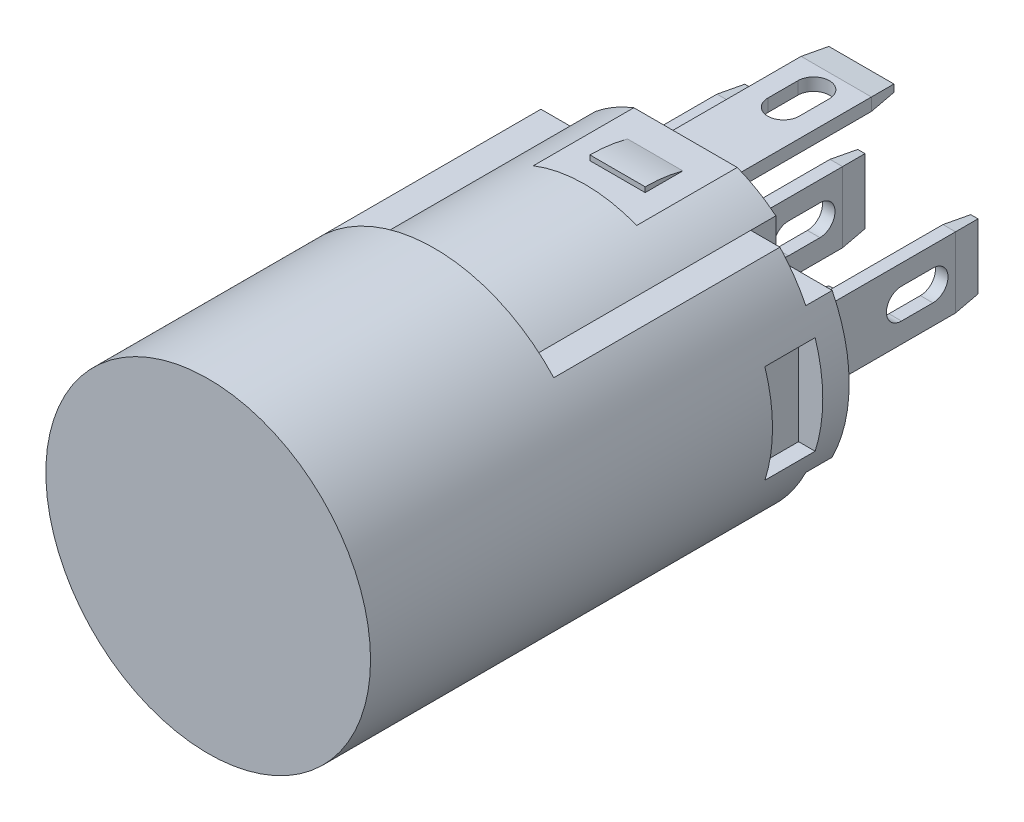
SolidWorks part; units mm, degrees
ref_plane "Front Plane" through (0, 0, 0) normal (0, 0, 1) x (1, 0, 0)
ref_plane "Top Plane" through (0, 0, 0) normal (0, 1, 0) x (1, 0, 0)
ref_plane "Right Plane" through (0, 0, 0) normal (1, 0, 0) x (0, 0, -1)
sketch "Sketch1" plane through (0, 0, 0) normal (0, 0, 1) x (1, 0, 0)
  circle A10 centre (0, 0) radius 6.4624
  dimension "D1" = 12.9248
extrude "Boss-Extrude1" add sketch "Sketch1" against normal blind 19
sketch "Sketch2" plane through (0, 0, -19) normal (0, 0, -1) x (-1, 0, 0)
  line L1 (-7.5854, -4.375) -> (7.5854, -4.375)
  line L2 (-7.5854, -4.375) -> (-7.5854, 4.375)
  line L3 (-7.5854, 4.375) -> (7.5854, 4.375)
  line L4 (7.5854, -4.375) -> (7.5854, 4.375)
  line L5 (-7.5854, -4.375) -> (7.5854, 4.375) construction
  line L6 (-7.5854, 4.375) -> (7.5854, -4.375) construction
  circle A3 centre (0, 0) radius 5.6624
  circle A4 centre (0, 0) radius 5.6624
  circle A5 centre (0, 0) radius 6.4624
  circle A6 centre (0, 0) radius 6.4624
  circle M4 centre (0, 0) radius 6.4624
  dimension "D2" = 8.75
  dimension "D1" = 0.8
  dimension "D3" = 0
extrude "Cut-Extrude1" cut sketch "Sketch2" against normal blind 10 contours A4 L3 M4 | A4 L1 M4 region at (4.1755, -4.4724, -19) region at (0, 6.365, -19)
sketch "Sketch3" plane through (0, 0, -19) normal (0, 0, -1) x (-1, 0, 0)
  line L0 (-4.2468, 1.4) -> (-4.7468, -1.4) construction
  line L1 (-0.25, -1.4) -> (0.25, -1.4)
  line L2 (-0.25, -1.4) -> (-0.25, 1.4)
  line L3 (-0.25, 1.4) -> (0.25, 1.4)
  line L4 (0.25, -1.4) -> (0.25, 1.4)
  line L5 (-0.25, -1.4) -> (0.25, 1.4) construction
  line L6 (-0.25, 1.4) -> (0.25, -1.4) construction
  line L7 (0, 3.7558) -> (0, 4.375) construction
  line L8 (4.2468, -1.4) -> (4.7468, -1.4)
  line L9 (4.2468, -1.4) -> (4.2468, 1.4)
  line L10 (4.2468, 1.4) -> (4.7468, 1.4)
  line L11 (4.7468, -1.4) -> (4.7468, 1.4)
  line L12 (4.2468, -1.4) -> (4.7468, 1.4) construction
  line L13 (4.2468, 1.4) -> (4.7468, -1.4) construction
  line L14 (-4.2468, -1.4) -> (-4.7468, 1.4) construction
  line L15 (-4.7468, -1.4) -> (-4.7468, 1.4)
  line L16 (-4.2468, 1.4) -> (-4.7468, 1.4)
  line L17 (-4.2468, -1.4) -> (-4.2468, 1.4)
  line L18 (-4.2468, -1.4) -> (-4.7468, -1.4)
  line L19 (-3.5947, -4.375) -> (3.5947, -4.375)
  line L20 (-4.2468, 0) -> (-2.8967, 0) construction
  line L25 (-1.4, -4.375) -> (1.4, -4.375)
  line L26 (-1.4, -4.375) -> (-1.4, -3.875)
  line L27 (-1.4, -3.875) -> (1.4, -3.875)
  line L28 (1.4, -4.375) -> (1.4, -3.875)
  line L30 (1.4, 4.375) -> (1.4, 3.875)
  line L31 (-1.4, 3.875) -> (1.4, 3.875)
  line L32 (-1.4, 4.375) -> (-1.4, 3.875)
  line L33 (-1.4, 4.375) -> (1.4, 4.375)
  point P0 (0, 0)
  point P8 (4.4968, 0)
  point P17 (-4.4968, 0)
  point P22 (0, -4.375)
  point P27 (0, -3.875)
  point P36 (0, 4.375)
  dimension "D1" = 2.8
  dimension "D2" = 0.5
  dimension "D3" = 0.5
  dimension "D4" = 3.9968
  dimension "D5" = 2.8
  dimension "D6" = 0.5
extrude "Boss-Extrude2" add sketch "Sketch3" along normal blind 7 separate body contours L18 L17 L16 L15 | L33 L32 L31 L30 | L19 L28 L27 L26 | L8 L11 L10 L9 | L1 L4 L3 L2 region at (0, 0, -19) region at (-4.4968, 0, -19) region at (4.4968, 0, -19) region at (0, -4.125, -19) region at (0, 4.125, -19)
chamfer "Chamfer1" distance 1 angle 6 4 edges at (-4.2468, 0, -26) (-4.4968, 1.4, -26) (-4.7468, 0, -26) (-4.4968, -1.4, -26) first distance on face at (-4.2468, 0, -22.5) first distance on face at (-4.4968, 1.4, -22.5) first distance on face at (-4.7468, 0, -22.5) first distance on face at (-4.4968, -1.4, -22.5)
chamfer "Chamfer2" distance 1 angle 6 4 edges at (4.7468, 0, -26) (4.4968, 1.4, -26) (4.2468, 0, -26) (4.4968, -1.4, -26) first distance on face at (4.7468, 0, -22.5) first distance on face at (4.4968, 1.4, -22.5) first distance on face at (4.2468, 0, -22.5) first distance on face at (4.4968, -1.4, -22.5)
chamfer "Chamfer3" distance 1 angle 6 4 edges at (0.25, 0, -26) (0, 1.4, -26) (-0.25, 0, -26) (0, -1.4, -26) first distance on face at (0.25, 0, -22.5) first distance on face at (0, 1.4, -22.5) first distance on face at (-0.25, 0, -22.5) first distance on face at (0, -1.4, -22.5)
chamfer "Chamfer4" distance 1 angle 6 4 edges at (-1.4, 4.125, -26) (0, 3.875, -26) (1.4, 4.125, -26) (0, 4.375, -26) first distance on face at (-1.4, 4.125, -22.5) first distance on face at (0, 3.875, -22.5) first distance on face at (1.4, 4.125, -22.5) first distance on face at (0, 4.375, -22.5)
chamfer "Chamfer5" distance 1 angle 6 4 edges at (1.4, -4.125, -26) (0, -3.875, -26) (-1.4, -4.125, -26) (0, -4.375, -26) first distance on face at (1.4, -4.125, -22.5) first distance on face at (0, -3.875, -22.5) first distance on face at (-1.4, -4.125, -22.5) first distance on face at (0, -4.375, -22.5)
sketch "Sketch4" plane through (4.7468, 0, 0) normal (1, 0, 0) x (0, 0, -1)
  line L0 (22.85, 0) -> (24.1, 0) construction
  line L1 (22.85, 0.6) -> (24.1, 0.6)
  line L2 (22.85, -0.6) -> (24.1, -0.6)
  line L3 (25, -1.4) -> (25, 1.4) construction
  arc A0 (22.85, 0.6) -> (22.85, -0.6) centre (22.85, 0) ccw
  arc A1 (24.1, -0.6) -> (24.1, 0.6) centre (24.1, 0) ccw
  point P3 (23.475, 0)
  dimension "D2" = 0.9
  dimension "D1" = 1.25
  dimension "D3" = 1.2
extrude "Cut-Extrude2" cut sketch "Sketch4" against normal blind 15
sketch "Sketch6" plane through (0, -4.375, 0) normal (0, -1, 0) x (1, 0, 0)
  line L0 (0, -24.1) -> (0, -22.9) construction
  line L1 (-0.625, -24.1) -> (-0.625, -22.9)
  line L2 (0.625, -24.1) -> (0.625, -22.9)
  line L3 (-1.4, -25) -> (1.4, -25) construction
  arc A0 (-0.625, -24.1) -> (0.625, -24.1) centre (0, -24.1) ccw
  arc A1 (0.625, -22.9) -> (-0.625, -22.9) centre (0, -22.9) ccw
  point P3 (0, -23.5)
  dimension "D1" = 1.25
  dimension "D2" = 1.2
  dimension "D3" = 0.9
extrude "Cut-Extrude3" cut sketch "Sketch6" against normal blind 15
sketch "Sketch7" plane through (0, 0, -19) normal (0, 0, -1) x (-1, 0, 0)
  line L0 (-3.5947, -4.375) -> (-3.5947, -2.875)
  line L1 (-5.7876, -2.875) -> (-3.5947, -2.875)
  line L3 (-5.7876, 2.875) -> (-3.5947, 2.875)
  line L7 (3.5947, 4.375) -> (3.5947, 2.875)
  line L8 (-3.5947, 2.875) -> (-3.5947, 4.375)
  line L11 (3.5947, -2.875) -> (3.5947, -4.375)
  line L12 (3.5947, 2.875) -> (5.7876, 2.875)
  line L13 (3.5947, -2.875) -> (5.7876, -2.875)
  line L16 (-3.5947, 4.375) -> (-4.7562, 4.375)
  line L17 (-4.7562, -4.375) -> (-3.5947, -4.375)
  line L18 (3.5947, -4.375) -> (4.7562, -4.375)
  line L19 (4.7562, 4.375) -> (3.5947, 4.375)
  line L20 (-3.5947, 4.375) -> (-4.7562, 4.375)
  line L21 (-4.7562, -4.375) -> (-3.5947, -4.375)
  line L22 (3.5947, -4.375) -> (4.7562, -4.375)
  line L23 (4.7562, 4.375) -> (3.5947, 4.375)
  arc A0 (5.7876, 2.875) -> (4.7562, 4.375) centre (0, 0) ccw
  arc A1 (-5.9696, -2.4752) -> (-4.7562, -4.375) centre (0, 0) ccw
  arc A4 (3.5947, 4.375) -> (-3.5947, 4.375) centre (0, 0) ccw
  arc A5 (-4.7562, 4.375) -> (-4.7562, -4.375) centre (0, 0) ccw
  arc A6 (-3.5947, -4.375) -> (3.5947, -4.375) centre (0, 0) ccw
  arc A7 (4.7562, -4.375) -> (4.7562, 4.375) centre (0, 0) ccw
  arc A8 (3.5947, 4.375) -> (-3.5947, 4.375) centre (0, 0) ccw
  arc A9 (-4.7562, 4.375) -> (-5.7876, 2.875) centre (0, 0) ccw
  arc A10 (-3.5947, -4.375) -> (3.5947, -4.375) centre (0, 0) ccw
  arc A11 (4.7562, -4.375) -> (5.7876, -2.875) centre (0, 0) ccw
  point P0 (0, 0)
  line M14 (-3.5947, 4.375) -> (-4.7562, 4.375)
  arc M15 (-4.7562, 4.375) -> (-4.7562, -4.375) centre (0, 0) ccw
  line M16 (-4.7562, -4.375) -> (-3.5947, -4.375)
  line M18 (3.5947, -4.375) -> (4.7562, -4.375)
  arc M19 (4.7562, -4.375) -> (4.7562, 4.375) centre (0, 0) ccw
  line M20 (4.7562, 4.375) -> (3.5947, 4.375)
  dimension "D1" = 1.5
  dimension "D3" = 1.5
  dimension "D2" = 0
extrude "Cut-Extrude4" cut sketch "Sketch7" against normal blind 1 contours L13 L11 M18 M19 | L1 L0 M15 M16 | L3 L8 M14 M15 | L7 L12 M19 M20 region at (4.4849, -3.5509, -19) region at (-4.4849, -3.5509, -19) region at (4.4849, 3.5509, -19) region at (-4.4849, 3.5509, -19)
sketch "Sketch8" plane through (0, 0, -19) normal (0, 0, -1) x (-1, 0, 0)
  line L0 (0.0065, -1010.55) -> (0.0065, -5.275) construction
  line L12 (-1.4, 4.375) -> (1.4, 4.375) construction
  line L13 (-4.435, 11.225) -> (4.448, 11.225)
  line L14 (-4.435, 11.225) -> (-4.435, 5.275)
  line L15 (-4.435, 5.275) -> (4.448, 5.275)
  line L16 (4.448, 11.225) -> (4.448, 5.275)
  line L17 (-4.435, 11.225) -> (4.448, 5.275) construction
  line L18 (-4.435, 5.275) -> (4.448, 11.225) construction
  line L19 (1.4, -4.375) -> (-1.4, -4.375) construction
  line L20 (-4.8319, -7.6535) -> (4.8449, -7.6535)
  line L21 (-4.8319, -7.6535) -> (-4.8319, -5.275)
  line L22 (-4.8319, -5.275) -> (4.8449, -5.275)
  line L23 (4.8449, -7.6535) -> (4.8449, -5.275)
  line L24 (-4.8319, -7.6535) -> (4.8449, -5.275) construction
  line L25 (-4.8319, -5.275) -> (4.8449, -7.6535) construction
  line L26 (0.0065, 5.275) -> (0.0065, 1007.9025) construction
  circle A0 centre (0, 0) radius 6.9 construction
  circle A1 centre (0, 0) radius 8.25 construction
  arc A2 (-5.6708, -4.375) -> (5.6708, -4.375) centre (0, 0) ccw construction
  point P1 (-6.8914, 0.3452)
  point P2 (0.0065, 8.25)
  point P24 (0.0065, -6.4642)
  dimension "D2" = 0.9
  dimension "D3" = 0.9
extrude "Cut-Extrude5" cut sketch "Sketch8" against normal blind 4
sketch "Sketch10" plane through (0, 0, -19) normal (0, 0, -1) x (-1, 0, 0)
  line L0 (-0.625, 2.875) -> (0.625, 2.875)
  line L1 (-0.625, -3.875) -> (0.625, -3.875)
  line L2 (-0.625, -3.875) -> (-0.625, -2.875)
  line L3 (-0.625, 3.875) -> (0.625, 3.875)
  line L4 (0.625, -3.875) -> (0.625, -2.875)
  line L5 (-0.625, -3.875) -> (-0.4637, -2.875) construction
  line L6 (-0.625, 3.875) -> (-0.4637, 2.875) construction
  line L7 (-0.625, -2.875) -> (0.625, -2.875)
  line L8 (0.625, 2.875) -> (0.625, 3.875)
  line L9 (0.4637, 2.875) -> (0.625, 3.875) construction
  line L10 (0.4637, -2.875) -> (0.625, -3.875) construction
  line L11 (-0.625, 2.875) -> (-0.625, 3.875)
  line L12 (-5.7876, -2.875) -> (-3.5947, -2.875) construction
  line L13 (-5.7876, 2.875) -> (-3.5947, 2.875) construction
  point P0 (0, 0)
extrude "Cut-Extrude6" cut sketch "Sketch10" against normal blind 0.3
sketch "Sketch11" plane through (0, 0, -19) normal (0, 0, -1) x (-1, 0, 0)
  line L0 (-5.7876, 2.875) -> (-3.5947, 2.875) construction
  line L1 (5.7876, -2.875) -> (-5.7876, -2.875)
  line L3 (5.7876, 2.875) -> (-5.7876, 2.875)
  line L5 (6.05, -0.9759) -> (-6.05, 0.9759) construction
  line L6 (6.05, 0.9759) -> (-6.05, -0.9759) construction
  line L17 (-3.5947, -2.875) -> (3.5947, -2.875)
  line L18 (3.5947, 2.875) -> (-3.5947, 2.875)
  line L19 (2.0584, 5.275) -> (-2.0584, 5.275)
  line L20 (2.0584, 5.275) -> (-2.0584, 5.275)
  line L21 (-2.0584, -5.275) -> (2.0584, -5.275)
  line L22 (-2.0584, -5.275) -> (2.0584, -5.275)
  line L28 (-5.7876, -2.875) -> (-3.5947, -2.875)
  line L29 (-3.5947, -2.875) -> (-3.5947, -4.375)
  line L30 (3.5947, -4.375) -> (3.5947, -2.875)
  line L31 (3.5947, -2.875) -> (5.7876, -2.875)
  line L33 (5.7876, 2.875) -> (3.5947, 2.875)
  line L34 (3.5947, 2.875) -> (3.5947, 4.375)
  line L35 (-3.5947, 4.375) -> (-3.5947, 2.875)
  line L36 (-3.5947, 2.875) -> (-5.7876, 2.875)
  line L38 (-5.7876, -2.875) -> (-3.5947, -2.875)
  line L41 (3.5947, -2.875) -> (5.7876, -2.875)
  line L43 (5.7876, 2.875) -> (3.5947, 2.875)
  line L46 (-3.5947, 2.875) -> (-5.7876, 2.875)
  arc A6 (-2.0584, 5.275) -> (-3.5947, 4.375) centre (0, 0) ccw
  arc A7 (-2.0584, 5.275) -> (-3.5947, 4.375) centre (0, 0) ccw
  arc A8 (2.0584, -5.275) -> (3.5947, -4.375) centre (0, 0) ccw
  arc A9 (2.0584, -5.275) -> (3.5947, -4.375) centre (0, 0) ccw
  arc A12 (-5.7876, 2.875) -> (-5.7876, -2.875) centre (0, 0) ccw
  arc A14 (-3.5947, -4.375) -> (-2.0584, -5.275) centre (0, 0) ccw
  arc A15 (5.7876, -2.875) -> (5.7876, 2.875) centre (0, 0) ccw
  arc A17 (3.5947, 4.375) -> (2.0584, 5.275) centre (0, 0) ccw
  arc A18 (-5.7876, 2.875) -> (-5.7876, -2.875) centre (0, 0) ccw
  arc A21 (5.7876, -2.875) -> (5.7876, 2.875) centre (0, 0) ccw
  point P0 (0, 0)
  line M7 (0.625, 2.875) -> (-0.625, 2.875)
  line M11 (-0.625, -2.875) -> (0.625, -2.875)
  arc M13 (-5.7876, 2.875) -> (-5.7876, -2.875) centre (0, 0) ccw
  arc M15 (-5.7876, 2.875) -> (-5.7876, -2.875) centre (0, 0) ccw
  line M16 (-5.7876, -2.875) -> (-3.5947, -2.875)
  line M20 (3.5947, -2.875) -> (5.7876, -2.875)
  arc M21 (5.7876, -2.875) -> (5.7876, 2.875) centre (0, 0) ccw
  arc M23 (5.7876, -2.875) -> (5.7876, 2.875) centre (0, 0) ccw
  line M24 (5.7876, 2.875) -> (3.5947, 2.875)
  line M28 (-3.5947, 2.875) -> (-5.7876, 2.875)
  dimension "D1" = 0
extrude "Boss-Extrude4" add sketch "Sketch11" along normal blind 0.05 contours L3 L1 M24 M7 M28 M13 M15 M16 M11 M20 M21 M23 region at (0, 0, -19)
sketch "Sketch12" plane through (0, 0, -19.05) normal (0, 0, -1) x (-1, 0, 0)
  line L8 (-4.7968, -1.45) -> (-4.1968, -1.45)
  line L9 (-4.1968, -1.45) -> (-4.1968, 1.45)
  line L10 (-4.1968, 1.45) -> (-4.7968, 1.45)
  line L11 (-4.7968, 1.45) -> (-4.7968, -1.45)
  line L12 (-4.7968, -1.45) -> (-4.1968, -1.45)
  line L13 (-4.1968, -1.45) -> (-4.1968, 1.45)
  line L14 (-4.1968, 1.45) -> (-4.7968, 1.45)
  line L15 (-4.7968, 1.45) -> (-4.7968, -1.45)
  line L20 (-0.3, 1.45) -> (-0.3, -1.45)
  line L21 (-0.3, -1.45) -> (0.3, -1.45)
  line L22 (0.3, -1.45) -> (0.3, 1.45)
  line L23 (0.3, 1.45) -> (-0.3, 1.45)
  line L24 (-0.3, 1.45) -> (-0.3, -1.45)
  line L25 (-0.3, -1.45) -> (0.3, -1.45)
  line L26 (0.3, -1.45) -> (0.3, 1.45)
  line L27 (0.3, 1.45) -> (-0.3, 1.45)
  line L32 (4.7968, -1.45) -> (4.7968, 1.45)
  line L33 (4.7968, 1.45) -> (4.1968, 1.45)
  line L34 (4.1968, 1.45) -> (4.1968, -1.45)
  line L35 (4.1968, -1.45) -> (4.7968, -1.45)
  line L36 (4.7968, -1.45) -> (4.7968, 1.45)
  line L37 (4.7968, 1.45) -> (4.1968, 1.45)
  line L38 (4.1968, 1.45) -> (4.1968, -1.45)
  line L39 (4.1968, -1.45) -> (4.7968, -1.45)
  line L44 (-1.45, 3.825) -> (1.45, 3.825)
  line L45 (1.45, 3.825) -> (1.45, 4.425)
  line L46 (1.45, 4.425) -> (-1.45, 4.425)
  line L47 (-1.45, 4.425) -> (-1.45, 3.825)
  line L48 (-1.45, 3.825) -> (1.45, 3.825)
  line L49 (1.45, 3.825) -> (1.45, 4.425)
  line L50 (1.45, 4.425) -> (-1.45, 4.425)
  line L51 (-1.45, 4.425) -> (-1.45, 3.825)
  line L56 (1.45, -4.425) -> (1.45, -3.825)
  line L57 (-1.45, -4.425) -> (1.45, -4.425)
  line L58 (1.45, -3.825) -> (-1.45, -3.825)
  line L59 (-1.45, -3.825) -> (-1.45, -4.425)
  line L60 (1.45, -4.425) -> (1.45, -3.825)
  line L61 (-1.45, -4.425) -> (1.45, -4.425)
  line L62 (1.45, -3.825) -> (-1.45, -3.825)
  line L63 (-1.45, -3.825) -> (-1.45, -4.425)
  dimension "D1" = 0.05
  dimension "D2" = 0.05
  dimension "D3" = 0.05
  dimension "D4" = 0.05
  dimension "D5" = 0.05
extrude "Cut-Extrude7" cut sketch "Sketch12" against normal mid plane 1
sketch "Sketch13" plane through (0, 0, -19) normal (0, 0, 1) x (1, 0, 0)
  line L0 (-0.25, -1.4) -> (0.25, -1.4) construction
  line L1 (0.25, -1.4) -> (0.25, 1.4) construction
  line L2 (0.25, 1.4) -> (-0.25, 1.4) construction
  line L3 (-0.25, 1.4) -> (-0.25, -1.4) construction
  line L4 (-4.7468, -1.4) -> (-4.2468, -1.4) construction
  line L5 (-4.2468, -1.4) -> (-4.2468, 1.4) construction
  line L6 (-4.2468, 1.4) -> (-4.7468, 1.4) construction
  line L7 (-4.7468, 1.4) -> (-4.7468, -1.4) construction
  line L8 (-1.4, -4.375) -> (1.4, -4.375) construction
  line L9 (1.4, -4.375) -> (1.4, -3.875) construction
  line L10 (1.4, -3.875) -> (-1.4, -3.875) construction
  line L11 (-1.4, -3.875) -> (-1.4, -4.375) construction
  line L12 (4.2468, -1.4) -> (4.7468, -1.4) construction
  line L13 (4.7468, -1.4) -> (4.7468, 1.4) construction
  line L14 (4.7468, 1.4) -> (4.2468, 1.4) construction
  line L15 (4.2468, 1.4) -> (4.2468, -1.4) construction
  line L16 (1.4, 4.375) -> (-1.4, 4.375) construction
  line L17 (-1.4, 4.375) -> (-1.4, 3.875) construction
  line L18 (-1.4, 3.875) -> (1.4, 3.875) construction
  line L19 (1.4, 3.875) -> (1.4, 4.375) construction
  line L20 (-0.25, -1.4) -> (0.25, -1.4)
  line L21 (0.25, -1.4) -> (0.25, 1.4)
  line L22 (0.25, 1.4) -> (-0.25, 1.4)
  line L23 (-0.25, 1.4) -> (-0.25, -1.4)
  line L24 (-4.7468, -1.4) -> (-4.2468, -1.4)
  line L25 (-4.2468, -1.4) -> (-4.2468, 1.4)
  line L26 (-4.2468, 1.4) -> (-4.7468, 1.4)
  line L27 (-4.7468, 1.4) -> (-4.7468, -1.4)
  line L28 (-1.4, -4.375) -> (1.4, -4.375)
  line L29 (1.4, -4.375) -> (1.4, -3.875)
  line L30 (1.4, -3.875) -> (-1.4, -3.875)
  line L31 (-1.4, -3.875) -> (-1.4, -4.375)
  line L32 (4.2468, -1.4) -> (4.7468, -1.4)
  line L33 (4.7468, -1.4) -> (4.7468, 1.4)
  line L34 (4.7468, 1.4) -> (4.2468, 1.4)
  line L35 (4.2468, 1.4) -> (4.2468, -1.4)
  line L36 (1.4, 4.375) -> (-1.4, 4.375)
  line L37 (-1.4, 4.375) -> (-1.4, 3.875)
  line L38 (-1.4, 3.875) -> (1.4, 3.875)
  line L39 (1.4, 3.875) -> (1.4, 4.375)
extrude "Boss-Extrude5" add sketch "Sketch13" along normal blind 0.5
sketch "Sketch15" plane through (0, 0, -19) normal (0, 0, -1) x (-1, 0, 0)
  line L0 (-5.7876, -2.875) -> (5.7876, -2.875) construction
  line L1 (2.3293, 3.575) -> (2.5293, 3.575)
  line L2 (2.3293, 3.575) -> (2.3293, 4.575)
  line L3 (2.3293, 4.575) -> (2.5293, 4.575)
  line L4 (2.5293, 3.575) -> (2.5293, 4.575)
  line L5 (2.3293, 3.575) -> (2.5293, 4.575) construction
  line L6 (2.3293, 4.575) -> (2.5293, 3.575) construction
  line L7 (1.9293, -4.175) -> (2.9293, -4.175)
  line L8 (1.9293, -4.175) -> (1.9293, -3.975)
  line L9 (1.9293, -3.975) -> (2.9293, -3.975)
  line L10 (2.9293, -4.175) -> (2.9293, -3.975)
  line L11 (1.9293, -4.175) -> (2.9293, -3.975) construction
  line L12 (1.9293, -3.975) -> (2.9293, -4.175) construction
  line L13 (2.3293, -4.575) -> (2.5293, -4.575)
  line L14 (2.3293, -4.575) -> (2.3293, -3.575)
  line L15 (2.3293, -3.575) -> (2.5293, -3.575)
  line L16 (2.5293, -4.575) -> (2.5293, -3.575)
  line L17 (2.3293, -4.575) -> (2.5293, -3.575) construction
  line L18 (2.3293, -3.575) -> (2.5293, -4.575) construction
  line L19 (5.7876, 2.875) -> (-5.7876, 2.875) construction
  point P0 (2.4293, 4.075)
  point P5 (2.4293, -4.075)
  point P10 (2.4293, -4.075)
  dimension "D1" = 0.2
  dimension "D2" = 0.2
  dimension "D3" = 1
  dimension "D4" = 1
  dimension "D5" = 0.7
  dimension "D6" = 0.7
  dimension "D7" = 0.2
  dimension "D8" = 1
extrude "Boss-Extrude6" add sketch "Sketch15" along normal blind 0.1 contours L7 L14 L9 L8 | L13 L16 L7 L14 | L16 L7 L10 L9 | L7 L16 L9 L14 | L9 L16 L15 L14 | L1 L4 L3 L2 region at (-2.4293, 4.075, -19) region at (-2.1293, -4.075, -19) region at (-2.4293, -4.075, -19) region at (-2.4293, -4.375, -19) region at (-2.7293, -4.075, -19) region at (-2.4293, -3.775, -19)
sketch "Sketch16" plane through (0, -5.275, 0) normal (0, -1, 0) x (1, 0, 0)
  line L0 (-2.0584, -19) -> (2.0584, -19) construction
  line L1 (-1.1047, -17.8) -> (1.0953, -17.8)
  line L2 (-1.1047, -17.8) -> (-1.1047, -16.3)
  line L3 (-1.1047, -16.3) -> (1.0953, -16.3)
  line L4 (1.0953, -17.8) -> (1.0953, -16.3)
  line L5 (-1.1047, -17.8) -> (1.0953, -16.3) construction
  line L6 (-1.1047, -16.3) -> (1.0953, -17.8) construction
  point P0 (-0.0047, -17.05)
  dimension "D1" = 2.2
  dimension "D2" = 1.5
  dimension "D3" = 1.2
extrude "Boss-Extrude7" add sketch "Sketch16" along normal blind 0.2
sketch "Sketch17" plane through (0, 5.275, 0) normal (0, 1, 0) x (1, 0, 0)
  line L4 (1.0953, 16.3) -> (1.0953, 17.8)
  line L5 (-1.1047, 16.3) -> (1.0953, 16.3)
  line L6 (-1.1047, 17.8) -> (-1.1047, 16.3)
  line L7 (1.0953, 17.8) -> (-1.1047, 17.8)
  line L8 (1.0953, 16.3) -> (1.0953, 17.8)
  line L9 (-1.1047, 16.3) -> (1.0953, 16.3)
  line L10 (-1.1047, 17.8) -> (-1.1047, 16.3)
  line L11 (1.0953, 17.8) -> (-1.1047, 17.8)
  dimension "D1" = 0
extrude "Boss-Extrude8" add sketch "Sketch17" along normal blind 0.2
fillet "Fillet2" radius 5.725 2 edges at (-0.0047, -5.475, -17.8) (-0.0047, 5.475, -17.8)
sketch "Sketch14" plane through (0, 0, -19.05) normal (0, 0, -1) x (-1, 0, 0)
  line L0 (-6.05, 0) -> (-2.2829, 0) construction
  line L2 (-4.7968, 1.45) -> (-4.7968, -1.45) construction
  line L4 (-4.3519, -1.2949) -> (-4.3519, 1.2949) construction
  line L5 (-4.6968, 2.25) -> (-3.6968, 2.25)
  line L6 (-4.8968, 2.05) -> (-4.8968, -2.05)
  line L7 (-4.6968, -2.25) -> (-3.2968, -2.25)
  line L8 (-3.4968, 2.05) -> (-3.4968, -0.05)
  line L9 (-3.2968, -2.25) -> (-2.7968, -2.25)
  line L10 (-2.5968, -2.05) -> (-2.5968, -0.45)
  line L11 (-2.7968, -0.25) -> (-3.2968, -0.25)
  line L13 (-4.1968, -1.45) -> (-4.1968, 1.45) construction
  line L17 (4.8968, 2.05) -> (4.8968, -2.05)
  line L18 (4.6968, -2.25) -> (3.6968, -2.25)
  line L22 (3.4968, 0.05) -> (3.4968, -0.05)
  line L23 (4.6968, 2.25) -> (3.6968, 2.25)
  line L24 (2.7968, 0.25) -> (3.2968, 0.25)
  line L25 (3.2968, 2.25) -> (2.7968, 2.25)
  line L26 (2.5968, 2.05) -> (2.5968, 0.45)
  line L27 (3.2968, 2.25) -> (3.6968, 2.25)
  line L28 (3.4968, -0.05) -> (3.4968, -2.05)
  line L29 (-1.7, 2.25) -> (0.2, 2.25)
  line L30 (0.4, 2.05) -> (0.4, -2.05)
  line L31 (0.2, -2.25) -> (-0.8, -2.25)
  line L32 (-1, -2.05) -> (-1, 0.05)
  line L33 (-1.2, 0.25) -> (-1.7, 0.25)
  line L34 (-1.9, 0.45) -> (-1.9, 2.05)
  line L35 (0.3, -1.45) -> (0.3, 1.45) construction
  line L36 (-0.3, 1.45) -> (-0.3, -1.45) construction
  arc A0 (-3.2968, -0.25) -> (-3.4968, -0.05) centre (-3.2968, -0.05) cw
  arc A1 (-2.5968, -0.45) -> (-2.7968, -0.25) centre (-2.7968, -0.45) ccw
  arc A2 (-2.7968, -2.25) -> (-2.5968, -2.05) centre (-2.7968, -2.05) ccw
  arc A3 (-4.8968, -2.05) -> (-4.6968, -2.25) centre (-4.6968, -2.05) ccw
  arc A4 (-3.6968, 2.25) -> (-3.4968, 2.05) centre (-3.6968, 2.05) cw
  arc A5 (-4.6968, 2.25) -> (-4.8968, 2.05) centre (-4.6968, 2.05) ccw
  arc A6 (4.8968, -2.05) -> (4.6968, -2.25) centre (4.6968, -2.05) cw
  arc A11 (4.6968, 2.25) -> (4.8968, 2.05) centre (4.6968, 2.05) cw
  arc A12 (3.2968, 0.25) -> (3.4968, 0.05) centre (3.2968, 0.05) cw
  arc A13 (2.5968, 0.45) -> (2.7968, 0.25) centre (2.7968, 0.45) ccw
  arc A14 (2.7968, 2.25) -> (2.5968, 2.05) centre (2.7968, 2.05) ccw
  arc A15 (3.4968, -2.05) -> (3.6968, -2.25) centre (3.6968, -2.05) ccw
  arc A16 (0.4, -2.05) -> (0.2, -2.25) centre (0.2, -2.05) cw
  arc A17 (-0.8, -2.25) -> (-1, -2.05) centre (-0.8, -2.05) cw
  arc A18 (-1, 0.05) -> (-1.2, 0.25) centre (-1.2, 0.05) ccw
  arc A19 (-1.7, 0.25) -> (-1.9, 0.45) centre (-1.7, 0.45) cw
  arc A20 (0.2, 2.25) -> (0.4, 2.05) centre (0.2, 2.05) cw
  arc A21 (-1.7, 2.25) -> (-1.9, 2.05) centre (-1.7, 2.05) ccw
  point P8 (-4.3519, 0)
  point P17 (-4.8968, 0)
  point P22 (-2.5968, -0.25)
  point P25 (-2.5968, -2.25)
  point P28 (-4.8968, -2.25)
  point P31 (-3.4968, 2.25)
  point P34 (-4.8968, 2.25)
  point P76 (0.4, -2.25)
  point P79 (-1, -2.25)
  point P84 (-1.9, 0.25)
  point P89 (-1.9, 2.25)
  dimension "D5" = 0.2
  dimension "D7" = 0.2
  dimension "D13" = 0.2
  dimension "D1" = 4.5
  dimension "D2" = 0.1
  dimension "D3" = 1.4
  dimension "D4" = 2
  dimension "D6" = 1.6
  dimension "D8" = 1.6
  dimension "D9" = 0.1
  dimension "D10" = 2
  dimension "D11" = 1.6
  dimension "D12" = 1.4
extrude "Cut-Extrude9" cut sketch "Sketch14" against normal blind 0.2
sketch "Sketch18" plane through (0, 0, 0) normal (1, 0, 0) x (0, 0, -1)
  line L0 (18, 2.875) -> (18, 4.375) construction
  line L1 (16, 1.9583) -> (18, 1.9583)
  line L2 (16, 1.9583) -> (16, -1.9583)
  line L3 (16, -1.9583) -> (18, -1.9583)
  line L4 (18, 1.9583) -> (18, -1.9583)
  line L5 (16, 1.9583) -> (18, -1.9583) construction
  line L6 (16, -1.9583) -> (18, 1.9583) construction
  point P0 (17, 0)
  dimension "D1" = 2
ref_plane "Plane1" through (10, 0, 0) normal (1, 0, 0) x (0, 0, -1)
sketch "Sketch19" plane through (10, 0, 0) normal (1, 0, 0) x (0, 0, -1)
  line L4 (18, 1.9583) -> (16, 1.9583)
  line L5 (18, -1.9583) -> (18, 1.9583)
  line L6 (16, -1.9583) -> (18, -1.9583)
  line L7 (16, 1.9583) -> (16, -1.9583)
  line L8 (18, 1.9583) -> (16, 1.9583)
  line L9 (18, -1.9583) -> (18, 1.9583)
  line L10 (16, -1.9583) -> (18, -1.9583)
  line L11 (16, 1.9583) -> (16, -1.9583)
  dimension "D1" = 0
extrude "Cut-Extrude10" cut sketch "Sketch19" against normal blind 4.5
mirror "Mirror1" about plane through (0, 0, 0) normal (1, 0, 0) of "Cut-Extrude10"
